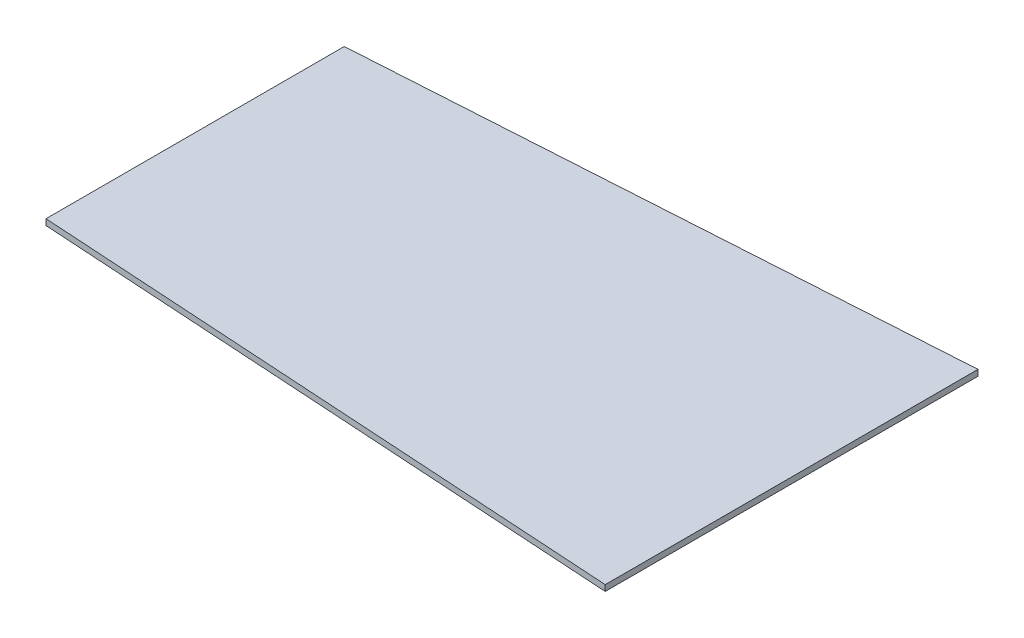
SolidWorks part; units mm, degrees
ref_plane "Front Plane" through (0, 0, 0) normal (0, 0, 1) x (1, 0, 0)
ref_plane "Top Plane" through (0, 0, 0) normal (0, 1, 0) x (1, 0, 0)
ref_plane "Right Plane" through (0, 0, 0) normal (1, 0, 0) x (0, 0, -1)
sketch "Sketch1" plane through (0, 0, 0) normal (0, 1, 0) x (1, 0, 0)
  line L0 (0, 0) -> (37.2605, 0) construction
  line L1 (-25.4, 12.7) -> (25.4, 15.875)
  line L2 (-25.4, 12.7) -> (-25.4, -12.7)
  line L3 (-25.4, -12.7) -> (25.4, -15.875)
  line L4 (25.4, 15.875) -> (25.4, -15.875)
  point P0 (0, 0)
  dimension "D1" = 50.8
  dimension "D2" = 25.4
  dimension "D3" = 31.75
base flange "Base-Flange1" sketch "Sketch1" thickness 0.508 reverse thickness direction no parameters "D1"=0.7366
sketch "Bend-Lines1" plane through (0, 0, 0) normal (0, 1, 0) x (1, 0, 0)
sketch "Bounding-Box1" plane through (0, 0, 0) normal (0, 1, 0) x (1, 0, 0)
sheet metal parameters "Sheet-Metal1" thickness 0.508 parameters "D1"=0.7366
flat pattern "Flat-Pattern1" [suppressed]
sketch "Bend-Lines2" plane through (0, 0, 0) normal (0, 1, 0) x (1, 0, 0)
sketch "Bounding-Box2" [suppressed] plane through (0, 0, 0) normal (0, 1, 0) x (1, 0, 0)
